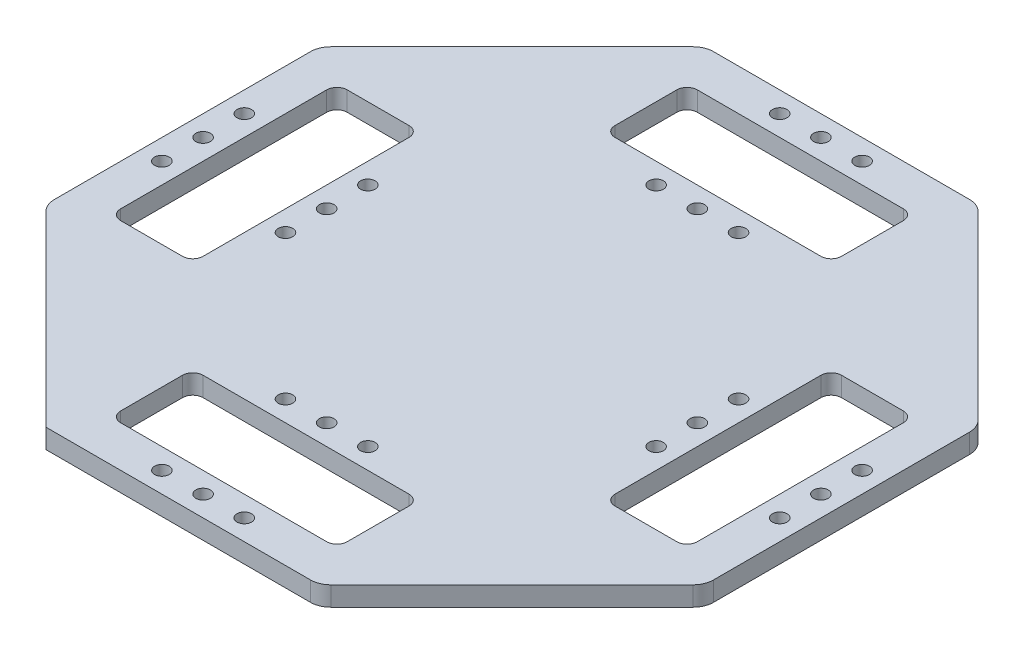
SolidWorks part; units mm, degrees
material "Custom Plastic"
ref_plane "Front Plane" through (0, 0, 0) normal (0, 0, 1) x (1, 0, 0)
ref_plane "Top Plane" through (0, 0, 0) normal (0, 1, 0) x (1, 0, 0)
ref_plane "Right Plane" through (0, 0, 0) normal (1, 0, 0) x (0, 0, -1)
ref_axis "Axis1" through (0, -0.2997, 0) along (0, 1, 0)
sketch "Base sketch" plane through (0, 0, 0) normal (0, 1, 0) x (1, 0, 0)
  line L1 (-101.6, 42.0841) -> (-101.6, -42.0841)
  line L2 (-101.6, -42.0841) -> (-42.0841, -101.6)
  line L3 (-42.0841, -101.6) -> (42.0841, -101.6)
  line L4 (42.0841, -101.6) -> (101.6, -42.0841)
  line L5 (101.6, -42.0841) -> (101.6, 42.0841)
  line L6 (101.6, 42.0841) -> (42.0841, 101.6)
  line L7 (42.0841, 101.6) -> (-42.0841, 101.6)
  line L8 (-42.0841, 101.6) -> (-101.6, 42.0841)
  circle A0 centre (0, 0) radius 101.6 construction
  dimension "D1" = 203.2
extrude "Base" add sketch "Base sketch" along normal blind 5.9944
sketch "Sketch3" plane through (0, 5.9944, 0) normal (0, 1, 0) x (1, 0, 0)
  line L0 (42.0841, 101.6) -> (-42.0841, 101.6) construction
  line L1 (-34.925, 88.9) -> (34.925, 88.9)
  line L2 (-34.925, 88.9) -> (-34.925, 63.5)
  line L4 (-34.925, 63.5) -> (34.925, 63.5)
  line L5 (34.925, 88.9) -> (34.925, 63.5)
  point P6 (0, 63.5)
  dimension "D1" = 69.85
  dimension "D2" = 25.4
  dimension "D3" = 12.7
extrude "Wheel cutout" cut sketch "Sketch3" against normal up to next
fillet "Wheel cutout fillets" radius 3.175 4 edges at (34.925, 2.9972, -88.9) (34.925, 2.9972, -63.5) (-34.925, 2.9972, -63.5) (-34.925, 2.9972, -88.9)
pattern_circular "Wheel cutout pattern" count 4 over 360 about axis through (0, -0.2997, 0) along (0, 1, 0) of "Wheel cutout", "Wheel cutout fillets"
fillet "Outside fillets" radius 6.35 7 edges at (-101.6, 2.9972, 42.0841) (-101.6, 2.9972, -42.0841) (-42.0841, 2.9972, -101.6) (42.0841, 2.9972, -101.6) (101.6, 2.9972, -42.0841) (101.6, 2.9972, 42.0841) (42.0841, 2.9972, 101.6)
hole_wizard "#8 Clearance Hole1" positions "Sketch7" profile "Sketch5" hole size "#8" standard "ANSI Inch" end condition up to next
sketch "Sketch7" plane through (0, 5.9944, 0) normal (0, 1, 0) x (1, 0, 0)
  line L0 (39.4538, 101.6) -> (-39.4538, 101.6) construction
  line L1 (-12.7, 95.25) -> (12.7, 95.25) construction
  line L2 (12.7, 57.15) -> (-12.7, 57.15) construction
  line L4 (31.75, 63.5) -> (-31.75, 63.5) construction
  point P0 (0, 95.25)
  point P2 (-12.7, 95.25)
  point P4 (12.7, 95.25)
  point P20 (12.7, 57.15)
  point P21 (-12.7, 57.15)
  point P31 (0, 57.15)
  dimension "D1" = 6.35
  dimension "D2" = 12.7
  dimension "D3" = 6.35
sketch "Sketch5" plane through (0, 5.9944, -95.25) normal (1, 0, 0) x (0, 0, 1)
  line L0 (0, 0) -> (0, 5.9954)
  line L1 (0, 5.9954) -> (2.2479, 5.9954)
  line L2 (2.2479, 5.9954) -> (2.2479, 0)
  line L5 (2.2479, 0) -> (0, 0)
  line L11 (0, -6.35) -> (0, 107.95) construction
  dimension "Thru Hole Dia." = 4.4958
  dimension "Thru Hole Depth" = 5.9954
pattern_circular "CirPattern2" count 4 over 360 about axis through (0, -0.2997, 0) along (0, 1, 0) of "#8 Clearance Hole1"
